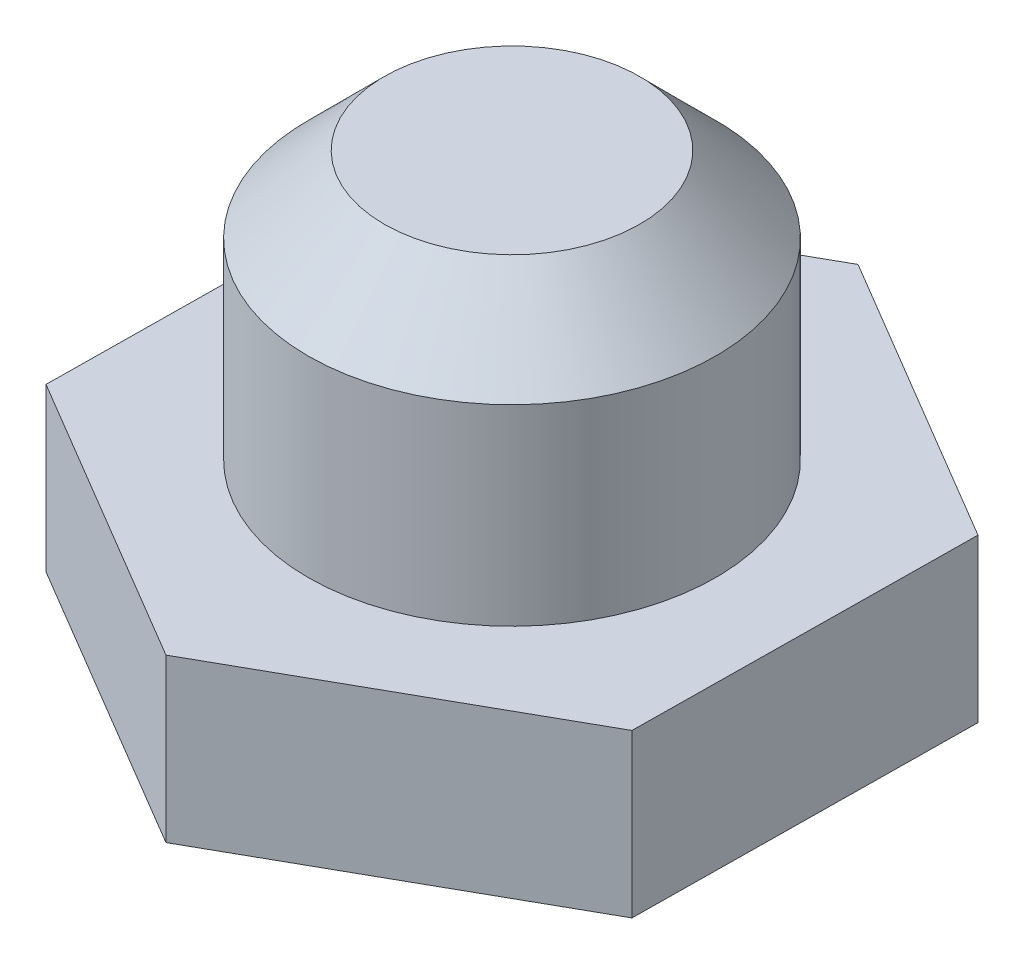
SolidWorks part; units mm, degrees
ref_plane "Front Plane" through (0, 0, 0) normal (0, 0, 1) x (1, 0, 0)
ref_plane "Top Plane" through (0, 0, 0) normal (0, 1, 0) x (1, 0, 0)
ref_plane "Right Plane" through (0, 0, 0) normal (1, 0, 0) x (0, 0, -1)
sketch "Sketch1" plane through (0, -69.088, -69.088) normal (0, 1, 0) x (1, 0, 0)
  line L1 (9.2098, -74.5453) -> (9.331, -63.8408)
  line L2 (9.331, -63.8408) -> (0.1213, -58.3835)
  line L3 (0.1213, -58.3835) -> (-9.2098, -63.6307)
  line L4 (-9.2098, -63.6307) -> (-9.331, -74.3352)
  line L5 (-9.331, -74.3352) -> (-0.1213, -79.7925)
  line L6 (-0.1213, -79.7925) -> (9.2098, -74.5453)
  circle A0 centre (0, -69.088) radius 9.271 construction
  circle A1 centre (0, -69.088) radius 6.3805
  circle A2 centre (0, -69.088) radius 6.1238
extrude "Boss-Extrude1" add sketch "Sketch1" along normal blind 8.382 contours A1
extrude "Boss-Extrude2" add sketch "Sketch1<11>" against normal blind 5.08 contours L3 L4 L5 L6 L1 L2
sketch "Sketch1<11>" plane through (0, -69.088, -69.088) normal (0, 1, 0) x (1, 0, 0) same geometry as "Sketch1"
chamfer "Chamfer1" distance 2.38 angle 45 1 edges at (0, -60.706, 6.3805)
